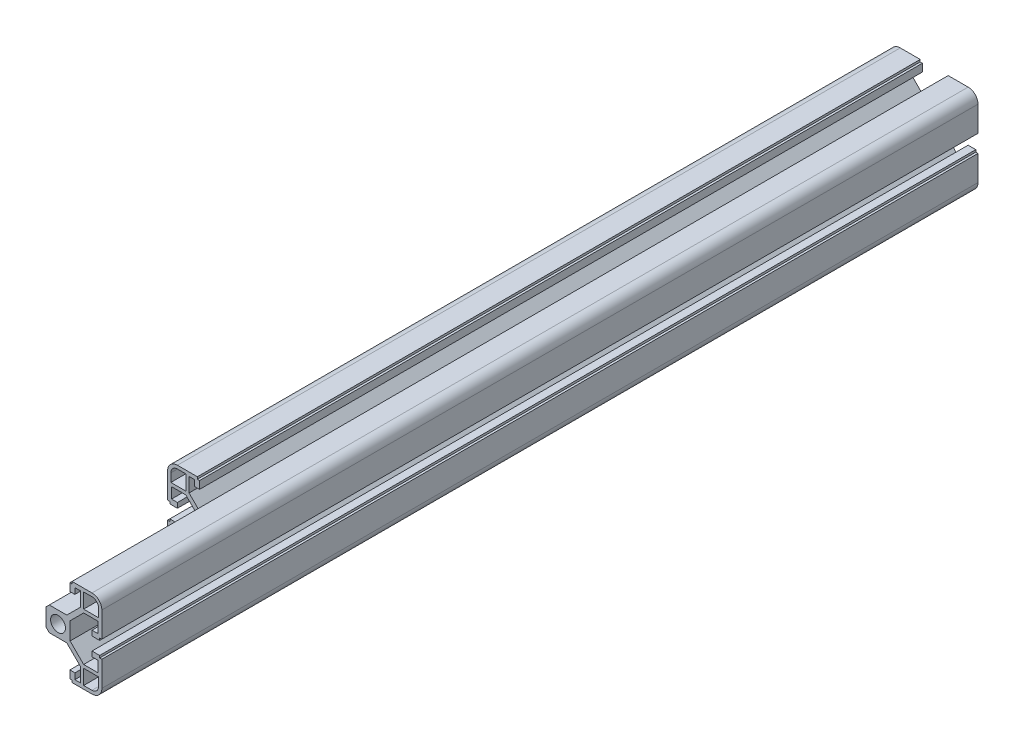
SolidWorks part; units mm, degrees
material "6061-T6 (SS)"
ref_plane "Front Plane" through (0, 0, 0) normal (0, 0, 1) x (1, 0, 0)
ref_plane "Top Plane" through (0, 0, 0) normal (0, 1, 0) x (1, 0, 0)
ref_plane "Right Plane" through (0, 0, 0) normal (1, 0, 0) x (0, 0, -1)
sketch "Sketch1" plane through (0, 0, 0) normal (0, 0, 1) x (1, 0, 0)
  line L0 (3.4, 0) -> (5.5, 0)
  line L1 (10.19, 11.69) -> (4, 5.5)
  line L2 (11.69, 10.19) -> (5.5, 4)
  line L3 (18.2, 10.19) -> (11.69, 10.19)
  line L4 (18.2, 10.19) -> (18.2, 5.2656)
  line L5 (18.2, 5.2656) -> (15.5, 5.2656)
  line L6 (15.5, 5.2656) -> (15.5, 2.9656)
  line L7 (15.5, 2.9656) -> (19, 2.9656)
  line L8 (19, 2.9656) -> (19, 3.9656)
  line L9 (19, 3.9656) -> (20, 3.9656)
  line L10 (20, 3.9656) -> (20, 15.5)
  line L11 (15.5, 20) -> (6.3853, 20)
  line L12 (18.5, 11.69) -> (18.5, 15.5)
  line L13 (15.5, 18.5) -> (11.69, 18.5)
  line L14 (11.69, 11.69) -> (11.69, 18.5)
  line L15 (0, 3.4) -> (0, 5.5)
  line L16 (4, 5.5) -> (0, 5.5)
  line L17 (6.3853, 20) -> (6.3853, 19)
  line L18 (5.5, 0) -> (5.5, 4)
  line L19 (6.3853, 19) -> (5.3853, 19)
  line L20 (5.3853, 19) -> (5.3853, 15.5)
  line L21 (5.3853, 15.5) -> (7.6853, 15.5)
  line L22 (10.19, 11.69) -> (10.19, 18.2)
  line L23 (11.69, 11.69) -> (18.5, 11.69)
  line L24 (7.6853, 18.2) -> (7.6853, 15.5)
  line L25 (10.19, 18.2) -> (7.6853, 18.2)
  arc A0 (20, 15.5) -> (15.5, 20) centre (15.5, 15.5) ccw
  arc A1 (18.5, 15.5) -> (15.5, 18.5) centre (15.5, 15.5) ccw
  arc A2 (3.4, 0) -> (0, 3.4) centre (0, 0) ccw
  dimension "D3" = 4.5
  dimension "D18" = 1.5
  dimension "D9" = 3.4
  dimension "D20" = 1.8
  dimension "D25" = 3
  dimension "D1" = 5.5
  dimension "D2" = 1.5
  dimension "D4" = 14.5
  dimension "D5" = 1.5
  dimension "D6" = 2.1
  dimension "D7" = 2.3
  dimension "D8" = 1.8
  dimension "D10" = 6.81
  dimension "D11" = 2.1
  dimension "D12" = 1
  dimension "D13" = 4.5
  dimension "D14" = 45
  dimension "D15" = 14.5
  dimension "D16" = 1
  dimension "D17" = 1.5
  dimension "D19" = 6.81
  dimension "D21" = 4.5
  dimension "D22" = 2.3
  dimension "D23" = 1
  dimension "D24" = 1
  dimension "D26" = 8.754
  dimension "D27" = 8.754
  dimension "D28" = 4.9244
  dimension "D29" = 2.5047
extrude "Boss-Extrude1" add sketch "Sketch1" along normal blind 400
mirror "Mirror1" about plane through (0, 0, 0) normal (0, 1, 0) of "Boss-Extrude1"
mirror "Mirror2" about plane through (0, 0, 0) normal (1, 0, 0) of "Boss-Extrude1"
mirror "Mirror3" about plane through (0, 0, 0) normal (0, 1, 0) of "Mirror2"
sketch "Croquis2" plane through (0, 0, 400) normal (0, 0, 1) x (1, 0, 0)
  line L0 (-4, 5.5) -> (-5.5, 4)
  line L1 (-5.5, 4) -> (-5.5, -4)
  line L2 (-5.5, -4) -> (-4, -5.5)
  line L3 (-4, -5.5) -> (-4, -28.3763)
  line L4 (-4, -28.3763) -> (-28.3763, -28.3763)
  line L5 (-28.3763, -28.3763) -> (-28.3763, 30.8262)
  line L6 (-28.3763, 30.8262) -> (-4, 30.8262)
  line L7 (-4, 30.8262) -> (-4, 5.5)
extrude "Cortar-Extruir2" cut sketch "Croquis2" against normal blind 70
